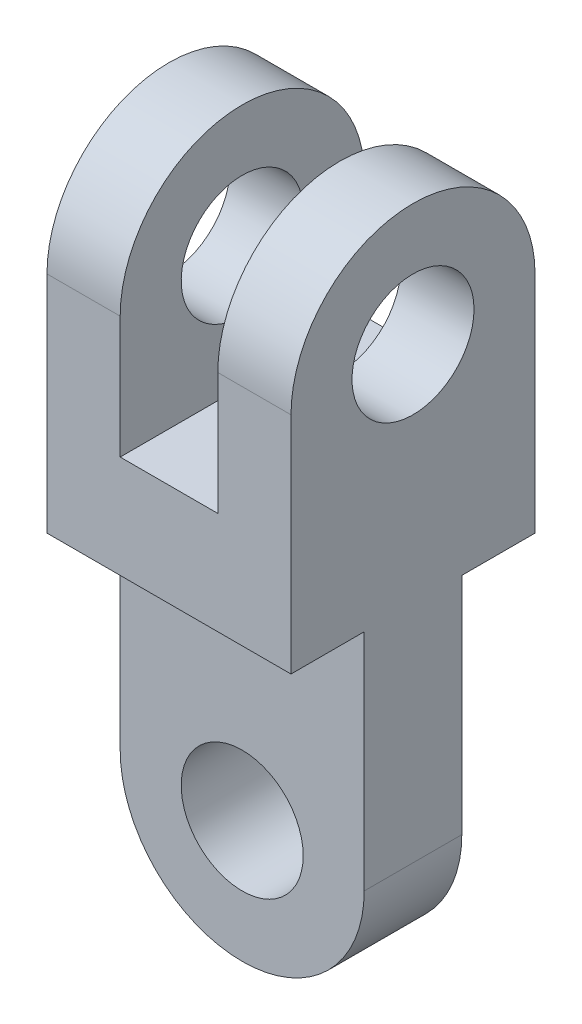
SolidWorks part; units mm, degrees
ref_plane "Alzado" through (0, 0, 0) normal (0, 0, 1) x (1, 0, 0)
ref_plane "Planta" through (0, 0, 0) normal (0, 1, 0) x (1, 0, 0)
ref_plane "Vista lateral" through (0, 0, 0) normal (1, 0, 0) x (0, 0, -1)
sketch "Croquis1" plane through (0, 0, 0) normal (0, 0, 1) x (1, 0, 0)
  line L0 (-50, 0) -> (-50, 92)
  line L1 (-50, 92) -> (50, 92)
  line L2 (50, 92) -> (50, 0)
  arc A0 (-50, 0) -> (50, 0) centre (0, 0) ccw
  circle A1 centre (0, 0) radius 25
  point P4 (0, -50)
  dimension "D1" = 50
  dimension "D3" = 50
  dimension "D2" = 142
extrude "Saliente-Extruir1" add sketch "Croquis1" against normal blind 40
sketch "Croquis2" plane through (0, 0, 0) normal (0, 0, 1) x (1, 0, 0)
  line L0 (-50, 92) -> (50, 92)
  line L1 (-50, 92) -> (-50, 184)
  line L2 (-50, 184) -> (-20, 184)
  line L3 (-20, 184) -> (-20, 134)
  line L4 (-20, 134) -> (20, 134)
  line L5 (20, 134) -> (20, 184)
  line L6 (20, 184) -> (50, 184)
  line L7 (50, 184) -> (50, 92)
  line L8 (-50, 184) -> (-50, 234)
  line L9 (-50, 234) -> (-20, 234)
  line L10 (-20, 234) -> (-20, 184)
  line L11 (20, 184) -> (20, 234)
  line L12 (20, 234) -> (50, 234)
  line L13 (50, 234) -> (50, 184)
  line M4 (50, 92) -> (-50, 92)
  dimension "D1" = 92
  dimension "D2" = 30
  dimension "D3" = 40
  dimension "D4" = 100
  dimension "D5" = 50
extrude "Saliente-Extruir2" add sketch "Croquis2" along normal blind 30 and the other way blind 70 contours L7 L6 L5 L4 L3 L2 L1 M4 | L10 L9 L8 L2 | L13 L12 L11 L6 region at (0, 132.1667, 0) region at (-35, 209, 0) region at (35, 209, 0)
fillet "Redondeo2" 2 edges at (-35, 234, 30) (-35, 234, -70) type full round first side face at (0, 173.5, 30) second side face at (0, 173.5, -70) middle face at (-35, 234, -20)
fillet "Redondeo3" 2 edges at (35, 234, 30) (35, 234, -70) type full round first side face at (0, 161, 30) second side face at (0, 161, -70) middle face at (35, 234, -20)
sketch "Croquis3" plane through (50, 0, 0) normal (1, 0, 0) x (0, 0, -1)
  line L7 (70, 92) -> (70, 184)
  line L8 (-30, 184) -> (-30, 92)
  line L9 (-30, 92) -> (0, 92)
  line L10 (0, 92) -> (0, 0)
  line L11 (0, 0) -> (40, 0)
  line L12 (40, 0) -> (40, 92)
  line L13 (40, 92) -> (70, 92)
  line L14 (70, 92) -> (70, 184)
  line L15 (-30, 184) -> (-30, 92)
  line L16 (-30, 92) -> (0, 92)
  line L17 (0, 92) -> (0, 0)
  line L18 (0, 0) -> (40, 0)
  line L19 (40, 0) -> (40, 92)
  line L20 (40, 92) -> (70, 92)
  circle A0 centre (20, 184) radius 25
  arc A1 (70, 184) -> (-30, 184) centre (20, 184) ccw
  arc A2 (70, 184) -> (-30, 184) centre (20, 184) ccw
  dimension "D2" = 50
  dimension "D1" = 0
extrude "Cortar-Extruir1" cut sketch "Croquis3" against normal through all contours A0
equation "\"A\"= 92mm"
equation "\"B\"= 142mm"
equation "\"D2@Croquis1\"=\"B\""
equation "\"D1@Croquis2\"=\"A\""
